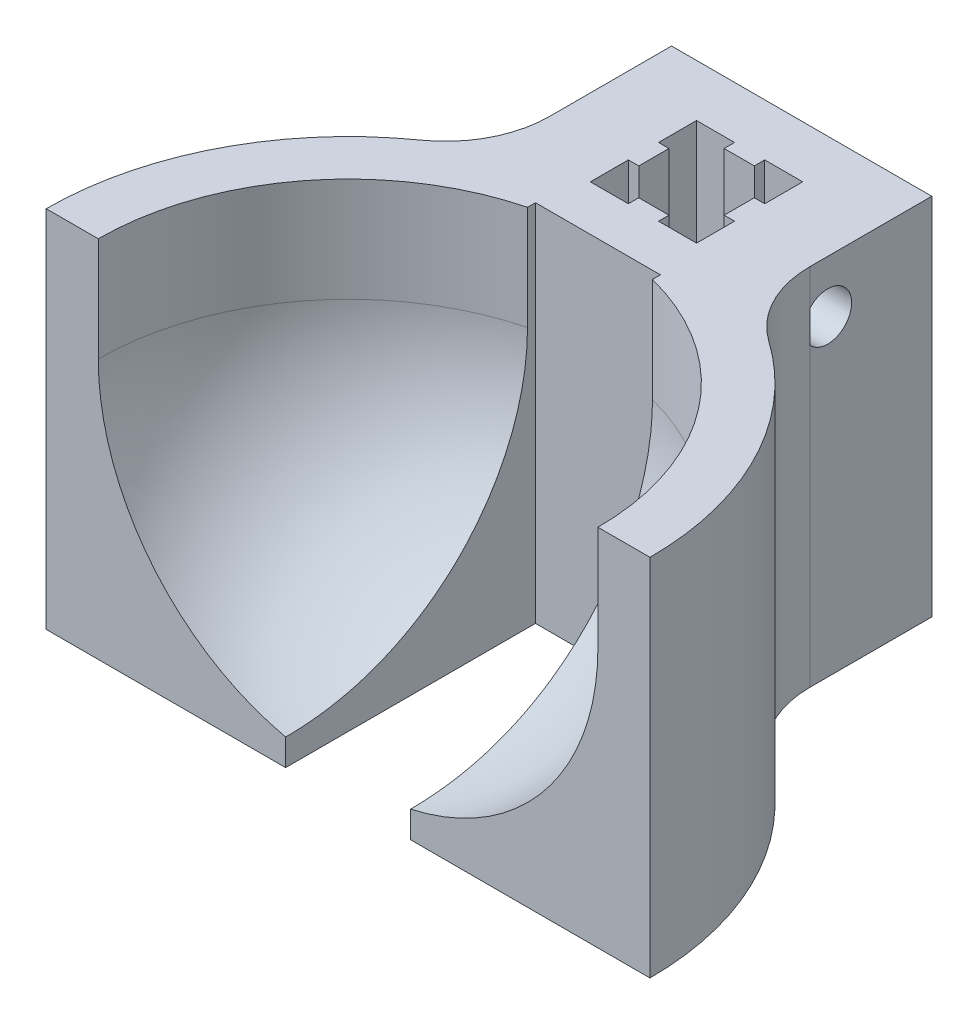
SolidWorks part; units mm, degrees
ref_plane "Front Plane" through (0, 0, 0) normal (0, 0, 1) x (1, 0, 0)
ref_plane "Top Plane" through (0, 0, 0) normal (0, 1, 0) x (1, 0, 0)
ref_plane "Right Plane" through (0, 0, 0) normal (1, 0, 0) x (0, 0, -1)
ref_axis "Axe1" through (0, -1.5691, 0) along (0, 1, 0)
sketch "Esquisse2" plane through (0, 0, 0) normal (-1, 0, 0) x (0, 0, 1)
  line L0 (-24, 35) -> (-29, 35)
  line L1 (-29, 35) -> (-29, 0)
  line L2 (-29, 0) -> (0, 0)
  line L3 (-1, 2) -> (0, 2)
  line L4 (-24, 35) -> (-24, 25)
  line L6 (0, 2) -> (0, 0)
  line L7 (0, -1.5691) -> (0, 32.9511) construction
  arc A0 (-24, 25) -> (-1, 2) centre (-1, 25) ccw
  dimension "D3" = 23
  dimension "D1" = 5
  dimension "D2" = 1
  dimension "D4" = 35
  dimension "D5" = 2
revolve "Révolution1" add sketch "Esquisse2" angle 180 mid plane about axis through (0, -1.5691, 0) along (0, 1, 0)
sketch "Esquisse3" plane through (0, 35, 0) normal (0, -1, 0) x (1, 0, 0)
  line L1 (-6, 0) -> (6, 0)
  line L2 (-6, 0) -> (-6, -24)
  line L3 (-6, -24) -> (6, -24)
  line L4 (6, 0) -> (6, -24)
  line L8 (-6, -28.3725) -> (6, -28.3725)
  line L9 (-6, -28.3725) -> (-6, -29)
  line L10 (-6, -29) -> (6, -29)
  line L11 (6, -28.3725) -> (6, -29)
  arc A0 (-29, 0) -> (29, 0) centre (0, 0) ccw construction
  arc A1 (-24, 0) -> (24, 0) centre (0, 0) ccw construction
  point P6 (0, 0)
  dimension "D1" = 12
extrude "Ball Hole" cut sketch "Esquisse3" along normal through all
sketch "Esquisse4" plane through (0, 0, 0) normal (0, -1, 0) x (-1, 0, 0)
  line L0 (-6, 28.3725) -> (6, 28.3725) construction
  line L1 (1.45, 28.3725) -> (5.1, 28.3725)
  line L2 (1.45, 28.3725) -> (1.45, 29.3725)
  line L3 (1.45, 29.3725) -> (-1.45, 29.3725)
  line L4 (-1.45, 28.3725) -> (-1.45, 29.3725)
  line L5 (5.1, 28.3725) -> (5.1, 32.0225)
  line L6 (5.1, 32.0225) -> (4.1, 32.0225)
  line L7 (4.1, 32.0225) -> (4.1, 34.9225)
  line L8 (4.1, 34.9225) -> (5.1, 34.9225)
  line L9 (5.1, 34.9225) -> (5.1, 38.5725)
  line L10 (5.1, 38.5725) -> (1.45, 38.5725)
  line L11 (1.45, 38.5725) -> (1.45, 37.5725)
  line L12 (1.45, 37.5725) -> (-1.45, 37.5725)
  line L13 (-1.45, 37.5725) -> (-1.45, 38.5725)
  line L14 (-1.45, 38.5725) -> (-5.1, 38.5725)
  line L15 (-5.1, 38.5725) -> (-5.1, 34.9225)
  line L16 (-5.1, 34.9225) -> (-4.1, 34.9225)
  line L17 (-4.1, 34.9225) -> (-4.1, 32.0225)
  line L18 (-4.1, 32.0225) -> (-5.1, 32.0225)
  line L19 (-5.1, 32.0225) -> (-5.1, 28.3725)
  line L20 (-5.1, 28.3725) -> (-1.45, 28.3725)
  line L21 (5.1, 32.0225) -> (12.5, 32.0225) construction
  line L22 (12.5, 24) -> (-12.5, 24)
  line L23 (12.5, 24) -> (12.5, 43.5725)
  line L24 (12.5, 43.5725) -> (-12.5, 43.5725)
  line L25 (-12.5, 24) -> (-12.5, 43.5725)
  line L26 (-5.1, 32.0225) -> (-12.5, 32.0225) construction
  line L27 (6, 24) -> (-6, 24) construction
  point P7 (0, 28.3725)
  point P40 (0, 29.3725)
  dimension "D1" = 2.9
  dimension "D2" = 1
  dimension "D3" = 10.2
  dimension "D4" = 10.2
  dimension "D5" = 5
  dimension "D6" = 25
extrude "Fixing Support" add sketch "Esquisse4" against normal through all
fillet "Congé1" radius 10 2 edges at (-12.5, 17.5, -26.1677) (12.5, 17.5, -26.1677)
sketch "Esquisse5" plane through (0, 0, -43.5725) normal (0, 0, -1) x (-1, 0, 0)
  line L3 (0, -1.5691) -> (0, 32.9511) construction
  line L4 (6, 0) -> (-6, 0) construction
  line L5 (6, 35) -> (-6, 35) construction
  circle A0 centre (0, 8) radius 1.6
  circle A1 centre (0, 27) radius 1.6
  dimension "D1" = 3.2
  dimension "D2" = 8
  dimension "D3" = 8
extrude "Fixing Hole" cut sketch "Esquisse5" against normal up to next
sketch "Esquisse7" plane through (0, 0, -43.5725) normal (0, 0, -1) x (-1, 0, 0)
  circle A0 centre (0, 27) radius 4.25
  circle A1 centre (0, 8) radius 4.25
  dimension "D1" = 8.5
extrude "Fixing Screw Hole" cut sketch "Esquisse7" against normal blind 2
sketch "Esquisse6" plane through (-12.5, 0, 0) normal (-1, 0, 0) x (0, 0, 1)
  line L2 (-43.5725, 35) -> (-43.5725, 0) construction
  line L3 (-31.8551, 35) -> (-43.5725, 35) construction
  circle A0 centre (-33.5725, 30) radius 2.3
  dimension "D1" = 4.6
  dimension "D2" = 10
  dimension "D3" = 5
extrude "Ressort Hole" cut sketch "Esquisse6" against normal blind 7
mirror "Symétrie1" about plane through (0, 0, 0) normal (1, 0, 0) of "Ressort Hole"
